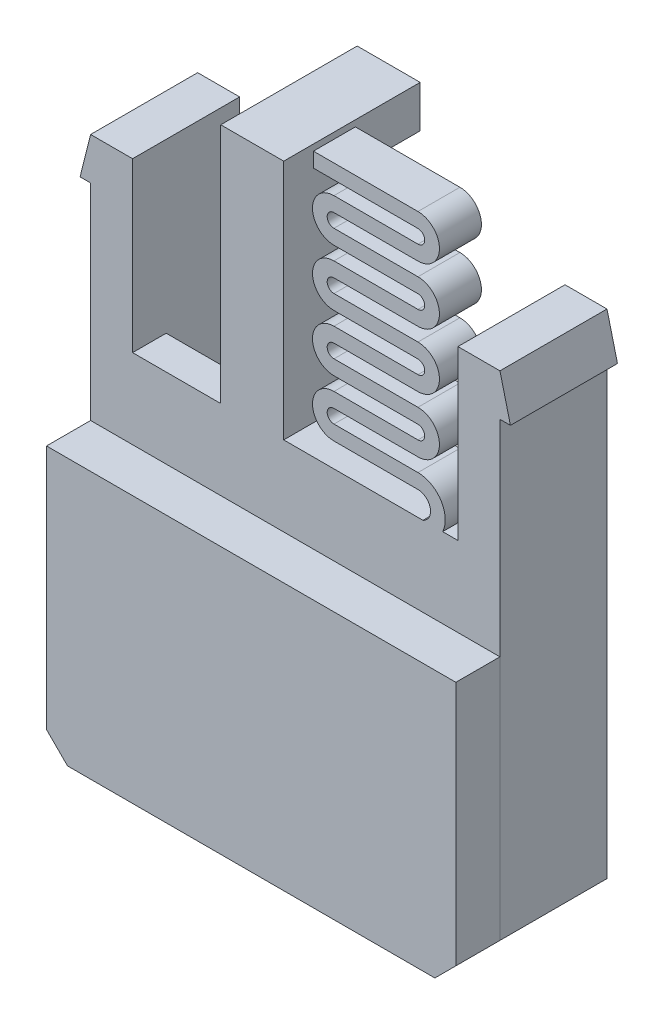
SolidWorks part; units mm, degrees
ref_plane "前视基准面" through (0, 0, 0) normal (0, 0, 1) x (1, 0, 0)
ref_plane "上视基准面" through (0, 0, 0) normal (0, 1, 0) x (1, 0, 0)
ref_plane "右视基准面" through (0, 0, 0) normal (1, 0, 0) x (0, 0, -1)
other "Configuration Table"
sketch "草图1" plane through (0, 0, 0) normal (0, 0, 1) x (1, 0, 0)
  line L0 (-63.9928, -19.7068) -> (-41.9928, -19.7068) construction
  line L1 (-62.7653, -7.0068) -> (-43.2653, -7.0068)
  line L2 (-62.7653, -7.0068) -> (-62.7653, -19.7068)
  line L3 (-62.7653, -19.7068) -> (-43.2653, -19.7068)
  line L4 (-43.2653, -7.0068) -> (-43.2653, -19.7068)
  dimension "D1" = 19.5
  dimension "D2" = 12.7
extrude "凸台-拉伸1" add sketch "草图1" along normal blind 2.1
sketch "草图2" plane through (0, 0, 0) normal (0, 0, -1) x (-1, 0, 0)
  line L1 (43.2653, -19.7068) -> (62.7653, -19.7068)
  line L2 (43.2653, -19.7068) -> (43.2653, 4.7932)
  line L3 (43.2653, 4.7932) -> (62.7653, 4.7932)
  line L4 (62.7653, -19.7068) -> (62.7653, 4.7932)
  dimension "D1" = 24.5
extrude "凸台-拉伸2" add sketch "草图2" along normal blind 5.1
sketch "草图3" plane through (0, 4.7932, 0) normal (0, 1, 0) x (1, 0, 0)
  line L0 (-62.7653, 5.1) -> (-43.2653, 5.1) construction
  line L1 (-60.7653, 5.1) -> (-45.2653, 5.1)
  line L2 (-60.7653, 5.1) -> (-60.7653, 1.6)
  line L3 (-60.7653, 1.6) -> (-45.2653, 1.6)
  line L4 (-45.2653, 5.1) -> (-45.2653, 1.6)
  line L5 (-62.7653, 5.1) -> (-62.7653, 0) construction
  line L6 (-43.2653, 5.1) -> (-43.2653, 0) construction
  dimension "D1" = 2
  dimension "D2" = 2
  dimension "D3" = 3.5
extrude "切除-拉伸1" cut sketch "草图3" against normal blind 23
sketch "草图4" plane through (0, 0, 0) normal (0, 0, 1) x (1, 0, 0)
  line L1 (-60.7653, 4.7932) -> (-45.2653, 4.7932)
  line L2 (-60.7653, 4.7932) -> (-60.7653, -3.2068)
  line L3 (-60.7653, -3.2068) -> (-45.2653, -3.2068)
  line L4 (-45.2653, 4.7932) -> (-45.2653, -3.2068)
  dimension "D1" = 8
extrude "切除-拉伸2" cut sketch "草图4" against normal up to next
sketch "草图5" plane through (0, 0, -5.1) normal (0, 0, -1) x (-1, 0, 0)
  line L0 (62.7653, 4.7932) -> (63.2653, 2.7932)
  line L1 (63.2653, 2.7932) -> (62.7653, 2.7932)
  line L2 (62.7653, -19.7068) -> (62.7653, 4.7932) construction
  line L3 (62.7653, 2.7932) -> (62.7653, 4.7932)
  line L4 (43.2653, 4.7932) -> (42.7653, 2.7932)
  line L5 (42.7653, 2.7932) -> (43.2653, 2.7932)
  line L6 (43.2653, 4.7932) -> (43.2653, -19.7068) construction
  line L7 (43.2653, 2.7932) -> (43.2653, 4.7932)
  dimension "D1" = 2
  dimension "D2" = 0.5
extrude "凸台-拉伸4" add sketch "草图5" against normal up to surface (5.1 mm away) up to face at (-53.0153, -0.1568, 0)
sketch "草图7" plane through (0, 0, 0) normal (0, 0, 1) x (1, 0, 0)
  line L0 (-47.1711, -1.7068) -> (-51.1711, -1.7068) construction
  line L1 (-60.7653, -3.2068) -> (-45.2653, -3.2068) construction
  line L2 (-47.1711, -0.3606) -> (-51.1711, -0.3606) construction
  line L3 (-47.1711, 0.9857) -> (-51.1711, 0.9857) construction
  line L4 (-47.1711, 2.3319) -> (-51.1711, 2.3319) construction
  line L5 (-47.1711, 3.6782) -> (-51.1711, 3.6782) construction
  line L6 (-47.1711, 5.0244) -> (-51.1711, 5.0244) construction
  line L7 (-47.1711, 6.3707) -> (-51.1711, 6.3707) construction
  line L8 (-47.1711, 7.7169) -> (-51.1711, 7.7169) construction
  line L9 (-47.1711, 9.0632) -> (-51.1711, 9.0632) construction
  line L10 (-47.1711, -1.3568) -> (-51.1711, -1.3568)
  line L11 (-47.1711, -0.7106) -> (-51.1711, -0.7106)
  line L12 (-47.1711, 1.3357) -> (-51.1711, 1.3357)
  line L13 (-47.1711, 1.9819) -> (-51.1711, 1.9819)
  line L14 (-47.1711, 4.0282) -> (-51.1711, 4.0282)
  line L15 (-47.1711, 4.6744) -> (-51.1711, 4.6744)
  line L16 (-47.1711, 6.7207) -> (-51.1711, 6.7207)
  line L17 (-47.1711, 7.3669) -> (-51.1711, 7.3669)
  line L18 (-47.1711, 9.4132) -> (-52.1509, 9.4132)
  line L19 (-47.1711, -2.0568) -> (-51.1711, -2.0568)
  line L20 (-47.1711, -0.0106) -> (-51.1711, -0.0106)
  line L21 (-47.1711, 0.6357) -> (-51.1711, 0.6357)
  line L22 (-47.1711, 2.6819) -> (-51.1711, 2.6819)
  line L23 (-47.1711, 3.3282) -> (-51.1711, 3.3282)
  line L24 (-47.1711, 5.3744) -> (-51.1711, 5.3744)
  line L25 (-47.1711, 6.0207) -> (-51.1711, 6.0207)
  line L26 (-47.1711, 8.0669) -> (-51.1711, 8.0669)
  line L27 (-47.1711, 8.7132) -> (-52.1509, 8.7132)
  line L28 (-47.1711, 9.0632) -> (-51.1407, 9.0632) construction
  line L29 (-47.1711, 8.7132) -> (-51.1407, 8.7132) construction
  line L30 (-47.1711, 9.4132) -> (-51.1407, 9.4132) construction
  line L31 (-72.3676, 9.4132) -> (-44.6127, 9.4132) construction
  line L32 (-52.1509, 9.4132) -> (-52.1509, 8.7132)
  line L33 (-46.9314, -3.2068) -> (-47.3969, -3.9371)
  arc A0 (-47.1711, -1.7068) -> (-46.3965, -3.2068) centre (-47.1711, -2.6568) cw construction
  arc A1 (-51.1711, -0.3606) -> (-51.1711, -1.7068) centre (-51.1711, -1.0337) ccw construction
  arc A2 (-47.1711, -0.3606) -> (-47.1711, 0.9857) centre (-47.1711, 0.3125) ccw construction
  arc A3 (-51.1711, 0.9857) -> (-51.1711, 2.3319) centre (-51.1711, 1.6588) cw construction
  arc A4 (-47.1711, 2.3319) -> (-47.1711, 3.6782) centre (-47.1711, 3.005) ccw construction
  arc A5 (-51.1711, 3.6782) -> (-51.1711, 5.0244) centre (-51.1711, 4.3513) cw construction
  arc A6 (-47.1711, 5.0244) -> (-47.1711, 6.3707) centre (-47.1711, 5.6975) ccw construction
  arc A7 (-51.1711, 6.3707) -> (-51.1711, 7.7169) centre (-51.1711, 7.0438) cw construction
  arc A8 (-47.1711, 7.7169) -> (-47.1711, 9.0632) centre (-47.1711, 8.39) ccw construction
  arc A9 (-47.1711, -1.3568) -> (-47.3969, -3.9371) centre (-47.1711, -2.6568) cw
  arc A10 (-51.1711, -0.7106) -> (-51.1711, -1.3568) centre (-51.1711, -1.0337) ccw
  arc A11 (-47.1711, -0.7106) -> (-47.1711, 1.3357) centre (-47.1711, 0.3125) ccw
  arc A12 (-51.1711, 1.3357) -> (-51.1711, 1.9819) centre (-51.1711, 1.6588) cw
  arc A13 (-47.1711, 1.9819) -> (-47.1711, 4.0282) centre (-47.1711, 3.005) ccw
  arc A14 (-51.1711, 4.0282) -> (-51.1711, 4.6744) centre (-51.1711, 4.3513) cw
  arc A15 (-47.1711, 4.6744) -> (-47.1711, 6.7207) centre (-47.1711, 5.6975) ccw
  arc A16 (-51.1711, 6.7207) -> (-51.1711, 7.3669) centre (-51.1711, 7.0438) cw
  arc A17 (-47.1711, 7.3669) -> (-47.1711, 9.4132) centre (-47.1711, 8.39) ccw
  arc A18 (-47.1711, -2.0568) -> (-46.9314, -3.2068) centre (-47.1711, -2.6568) cw
  arc A19 (-51.1711, -0.0106) -> (-51.1711, -2.0568) centre (-51.1711, -1.0337) ccw
  arc A20 (-47.1711, -0.0106) -> (-47.1711, 0.6357) centre (-47.1711, 0.3125) ccw
  arc A21 (-51.1711, 0.6357) -> (-51.1711, 2.6819) centre (-51.1711, 1.6588) cw
  arc A22 (-47.1711, 2.6819) -> (-47.1711, 3.3282) centre (-47.1711, 3.005) ccw
  arc A23 (-51.1711, 3.3282) -> (-51.1711, 5.3744) centre (-51.1711, 4.3513) cw
  arc A24 (-47.1711, 5.3744) -> (-47.1711, 6.0207) centre (-47.1711, 5.6975) ccw
  arc A25 (-51.1711, 6.0207) -> (-51.1711, 8.0669) centre (-51.1711, 7.0438) cw
  arc A26 (-47.1711, 8.0669) -> (-47.1711, 8.7132) centre (-47.1711, 8.39) ccw
  arc A27 (-47.1711, -1.7068) -> (-47.3361, -3.5924) centre (-47.1711, -2.6568) cw construction
  arc A28 (-47.1711, -2.0568) -> (-47.2753, -3.2477) centre (-47.1711, -2.6568) cw construction
  dimension "D1" = 4
  dimension "D2" = 1.5
  dimension "D4" = 0.35
  dimension "D5" = 0.35
  dimension "D3" = 9
extrude "凸台-拉伸5" add sketch "草图7" against normal blind 2
sketch "草图8" plane through (0, -3.2068, 0) normal (0, 1, 0) x (1, 0, 0)
  line L0 (-60.7653, 0) -> (-46.9314, 0) construction
  line L1 (-56.5653, 0) -> (-53.5653, 0)
  line L2 (-56.5653, 0) -> (-56.5653, 3)
  line L3 (-56.5653, 3) -> (-53.5653, 3)
  line L4 (-53.5653, 0) -> (-53.5653, 3)
  line L5 (-60.7653, 1.6) -> (-60.7653, 0) construction
  dimension "D1" = 4.2
  dimension "D2" = 3
  dimension "D3" = 3
extrude "凸台-拉伸6" add sketch "草图8" along normal blind 11.5 and the other way blind 4
sketch "草图9" plane through (0, 0, -3) normal (0, 0, -1) x (-1, 0, 0)
  line L0 (56.5653, -7.2068) -> (56.5653, 8.2932) construction
  line L1 (53.5653, 8.2932) -> (56.5653, 8.2932)
  line L2 (53.5653, 8.2932) -> (53.5653, 6.2932)
  line L3 (53.5653, 6.2932) -> (56.5653, 6.2932)
  line L4 (56.5653, 8.2932) -> (56.5653, 6.2932)
  dimension "D1" = 2
extrude "凸台-拉伸7" add sketch "草图9" along normal blind 3.5
chamfer "倒角1" distance 1 angle 45 2 edges at (-62.7653, -19.7068, -1.5) (-43.2653, -19.7068, -1.5)
split "分割1" bodies to split 114 resulting bodies 115 116 split by face at (-50.3799, 2.7132, 0)
